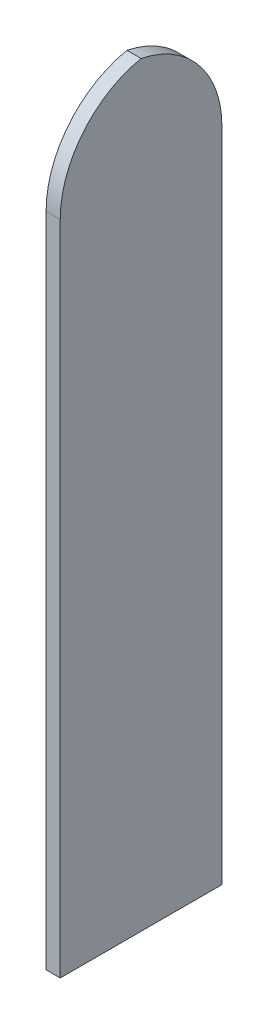
SolidWorks part; units mm, degrees
ref_plane "Front Plane" through (0, 0, 0) normal (0, 0, 1) x (1, 0, 0)
ref_plane "Top Plane" through (0, 0, 0) normal (0, 1, 0) x (1, 0, 0)
ref_plane "Right Plane" through (0, 0, 0) normal (1, 0, 0) x (0, 0, -1)
sketch "Sketch1" plane through (0, 0, 0) normal (1, 0, 0) x (0, 0, -1)
  line L1 (-8, -37.5) -> (8, -37.5)
  line L2 (-8, -37.5) -> (-8, 37.5)
  line L3 (-8, 37.5) -> (8, 37.5)
  line L4 (8, -37.5) -> (8, 37.5)
  line L5 (-8, -37.5) -> (8, 37.5) construction
  line L6 (-8, 37.5) -> (8, -37.5) construction
  point P0 (0, 0)
  dimension "D1" = 75
  dimension "D2" = 16
extrude "Boss-Extrude4" add sketch "Sketch1" along normal blind 1.4
fillet "Fillet1" radius 10 2 edges at (0.7, 37.5, 8) (0.7, 37.5, -8)
